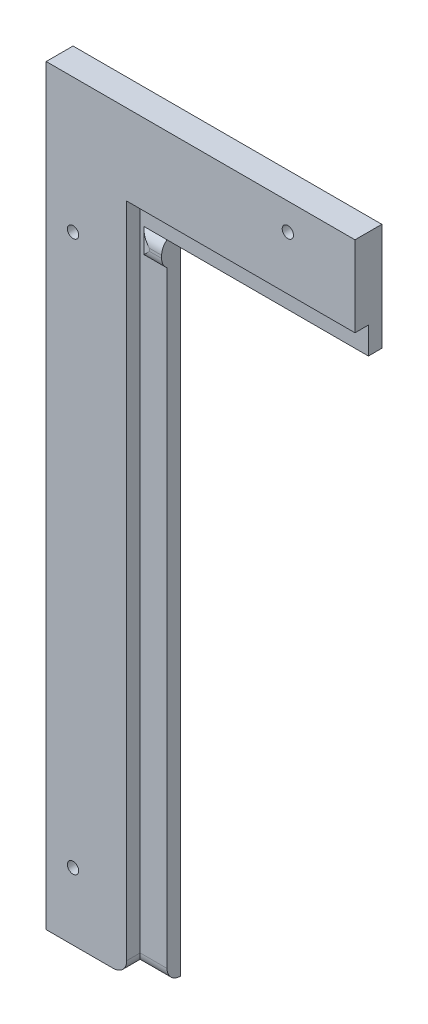
SolidWorks part; units mm, degrees
material "PLA+"
ref_plane "Front Plane" through (0, 0, 0) normal (0, 0, 1) x (1, 0, 0)
ref_plane "Top Plane" through (0, 0, 0) normal (0, 1, 0) x (1, 0, 0)
ref_plane "Right Plane" through (0, 0, 0) normal (1, 0, 0) x (0, 0, -1)
sketch "Sketch4" plane through (0, 0, 0) normal (0, 0, 1) x (1, 0, 0)
  line L1 (15, 125) -> (-15, 125)
  line L2 (15, 125) -> (15, -125)
  line L3 (15, -125) -> (-15, -125)
  line L4 (-15, 125) -> (-15, -125)
  line L5 (15, 125) -> (-15, -125) construction
  line L6 (15, -125) -> (-15, 125) construction
  line L11 (-15, 125) -> (100, 125)
  line L12 (-15, 125) -> (-15, 155)
  line L13 (-15, 155) -> (100, 155)
  line L14 (100, 125) -> (100, 155)
  point P0 (0, 0)
  dimension "D1" = 30
  dimension "D2" = 30
  dimension "D3" = 250
  dimension "D4" = 85
extrude "Boss-Extrude3" add sketch "Sketch4" along normal mid plane 10 contours L11 L14 L13 L12 L1 | L1 L4 L3 L2 region at (0, 0, 0) region at (42.5, 140, 0)
ref_plane "Plane1" through (15, 125, -5) normal (0, -1, 0) x (-1, 0, 0)
sketch "Sketch5" plane through (15, 125, -5) normal (0, -1, 0) x (1, 0, 0)
  line L0 (85, 10) -> (85, 0) construction
  line L1 (0, 0) -> (85, 0)
  line L2 (0, 0) -> (0, 5)
  line L3 (0, 5) -> (85, 5)
  line L4 (85, 0) -> (85, 5)
  dimension "D1" = 5
extrude "Boss-Extrude4" add sketch "Sketch5" along normal blind 10
sketch "Sketch6" plane through (15, 0, 0) normal (1, 0, 0) x (0, 0, -1)
  line L0 (-5, -125) -> (5, -125) construction
  line L1 (5, 115) -> (0, 115)
  line L2 (5, 115) -> (5, -125)
  line L3 (5, -125) -> (0, -125)
  line L4 (0, 115) -> (0, -125)
extrude "Boss-Extrude5" add sketch "Sketch6" along normal blind 10
sketch "Sketch7" plane through (0, 0, 0) normal (0, 0, 1) x (1, 0, 0)
  line L1 (25, 115) -> (16.5, 115)
  line L2 (25, 115) -> (25, 106)
  line L3 (25, 106) -> (16.5, 106)
  line L4 (16.5, 115) -> (16.5, 106)
  dimension "D1" = 9
  dimension "D2" = 8.5
extrude "Boss-Extrude6" add sketch "Sketch7" along normal blind 2
fillet "Fillet2" radius 5 3 edges at (16.5, 110.5, 2) (20.75, 115, 2) (20.75, 106, 2)
fillet "Fillet3" radius 5 2 edges at (15, -125, 2.5) (20, -125, 0)
sketch "Sketch8" plane through (0, 0, -5) normal (0, 0, -1) x (-1, 0, 0)
  line L0 (-100, 115) -> (-100, 155) construction
  line L1 (15, 155) -> (-100, 155) construction
  line L2 (15, -125) -> (15, 155) construction
  line L3 (-10, -125) -> (15, -125) construction
  circle A0 centre (5, -100) radius 2.1
  circle A1 centre (5, 105) radius 2.1
  circle A2 centre (-75, 145) radius 2.1
  dimension "D3" = 4.2
  dimension "D4" = 4.2
  dimension "D9" = 4.2
  dimension "D1" = 25
  dimension "D2" = 10
  dimension "D5" = 10
  dimension "D6" = 50
  dimension "D7" = 25
  dimension "D8" = 10
extrude "Cut-Extrude1" cut sketch "Sketch8" against normal blind 432
sketch "Sketch9" plane through (0, 0, -5) normal (0, 0, -1) x (-1, 0, 0)
  circle A0 centre (-75, 145) radius 3.6
  circle A2 centre (5, 105) radius 3.6
  circle A3 centre (5, -100) radius 3.6
  dimension "D1" = 7.2
  dimension "D2" = 7.2
  dimension "D3" = 7.2
extrude "Cut-Extrude2" cut sketch "Sketch9" against normal blind 4
